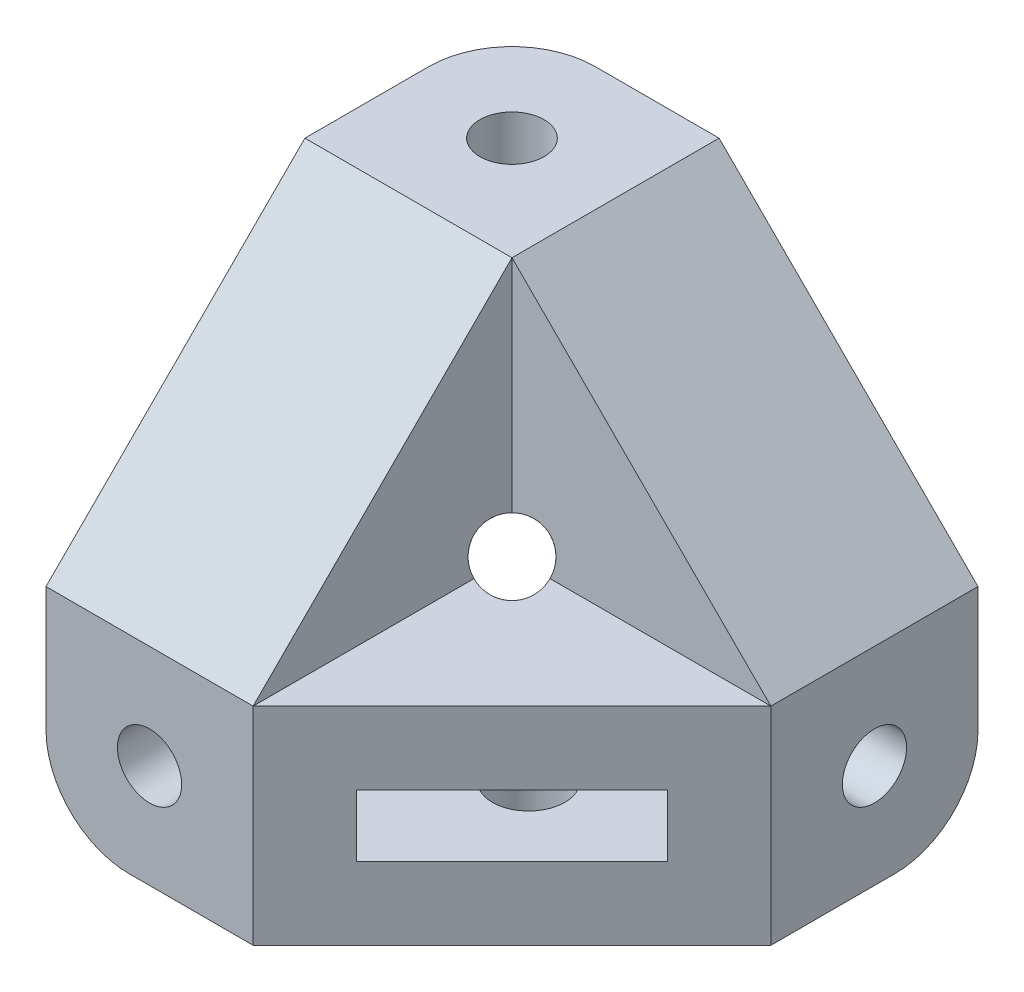
SolidWorks part; units mm, degrees
ref_plane "Front Plane" through (0, 0, 0) normal (0, 0, 1) x (1, 0, 0)
ref_plane "Top Plane" through (0, 0, 0) normal (0, 1, 0) x (1, 0, 0)
ref_plane "Right Plane" through (0, 0, 0) normal (1, 0, 0) x (0, 0, -1)
ref_plane "Plano1" through (0, 0, 20) normal (0, 0, 1) x (1, 0, 0)
sketch "Esboço1" plane through (0, 0, 20) normal (0, 0, 1) x (1, 0, 0)
  line L0 (9.638, 11.6423) -> (9.638, 56.6423)
  line L1 (9.638, 56.6423) -> (-35.362, 56.6423)
  line L2 (-35.362, 56.6423) -> (-35.362, 11.6423)
  line L3 (-35.362, 11.6423) -> (9.638, 11.6423)
extrude "Ressalto-extrusão1" add sketch "Esboço1" against normal blind 20
sketch "Esboço2" plane through (0, 0, 0) normal (0, 0, -1) x (-1, 0, 0)
  line L0 (15.362, 31.6423) -> (15.362, 56.6423)
  line L1 (15.362, 56.6423) -> (-9.638, 56.6423)
  line L2 (-9.638, 56.6423) -> (-9.638, 31.6423)
  line L3 (-9.638, 31.6423) -> (15.362, 31.6423)
extrude "Corte-extrusão1" cut sketch "Esboço2" against normal through all
sketch "Esboço3" plane through (0, 0, 20) normal (0, 0, 1) x (1, 0, 0)
  line L0 (-35.362, 31.6423) -> (-15.362, 31.6423)
  line L1 (-15.362, 31.6423) -> (-15.362, 11.6423)
  line L2 (-15.362, 11.6423) -> (-35.362, 11.6423)
  line L3 (-35.362, 11.6423) -> (-35.362, 31.6423)
extrude "Ressalto-extrusão2" add sketch "Esboço3" along normal blind 25
hole_wizard "Furo de diâmetro Ø6.2 (6.2)1" positions "Esboço5" profile "Esboço4" hole size "Ø6.2" standard "Ansi Metric"
sketch "Esboço5" plane through (9.638, 0, 0) normal (1, 0, 0) x (0, 0, -1)
  point P0 (-10, 21.6423)
sketch "Esboço4" plane through (9.638, 21.6423, 10) normal (0, 1, 0) x (0, 0, -1)
  line L0 (0, 0) -> (0, 35)
  line L1 (0, 35) -> (3.1, 35)
  line L2 (3.1, 35) -> (3.1, 0)
  line L5 (3.1, 0) -> (0, 0)
  line L10 (0, 35) -> (-3.1, 35) construction
  line L11 (0, -6.35) -> (0, 107.95) construction
  dimension "Hole Dia." = 6.2
  dimension "Hole Depth" = 35
  dimension "Drill Angle" = 180
hole_wizard "Furo de diâmetro Ø6.2 (6.2)2" positions "Esboço7" profile "Esboço6" hole size "Ø6.2" standard "Ansi Metric"
sketch "Esboço7" plane through (0, 56.6423, 0) normal (0, 1, 0) x (1, 0, 0)
  point P0 (-25.362, -10)
sketch "Esboço6" plane through (-25.362, 56.6423, 10) normal (1, 0, 0) x (0, 0, 1)
  line L0 (0, 0) -> (0, 35)
  line L1 (0, 35) -> (3.1, 35)
  line L2 (3.1, 35) -> (3.1, 0)
  line L5 (3.1, 0) -> (0, 0)
  line L10 (0, 35) -> (-3.1, 35) construction
  line L11 (0, -6.35) -> (0, 107.95) construction
  dimension "Hole Dia." = 6.2
  dimension "Hole Depth" = 35
  dimension "Drill Angle" = 180
hole_wizard "Furo de diâmetro Ø6.2 (6.2)3" positions "Esboço9" profile "Esboço8" hole size "Ø6.2" standard "Ansi Metric"
sketch "Esboço9" plane through (0, 0, 45) normal (0, 0, 1) x (1, 0, 0)
  point P0 (-25.362, 21.6423)
sketch "Esboço8" plane through (-25.362, 21.6423, 45) normal (1, 0, 0) x (0, -1, 0)
  line L0 (0, 0) -> (0, 35)
  line L1 (0, 35) -> (3.1, 35)
  line L2 (3.1, 35) -> (3.1, 0)
  line L5 (3.1, 0) -> (0, 0)
  line L10 (0, 35) -> (-3.1, 35) construction
  line L11 (0, -6.35) -> (0, 107.95) construction
  dimension "Hole Dia." = 6.2
  dimension "Hole Depth" = 35
  dimension "Drill Angle" = 180
fillet "Filete1" [suppressed] radius 4
fillet "Filete2" radius 8 3 edges at (-12.862, 11.6423, 0) (-35.362, 34.1423, 0) (-35.362, 11.6423, 22.5)
chamfer "Chanfro1" distance 25 angle 45 1 edges at (-25.362, 31.6423, 20)
chamfer "Chanfro2" distance 25 angle 45 1 edges at (-15.362, 31.6423, 10)
sketch "Esboço10" plane through (0, 11.6423, 0) normal (0, -1, 0) x (1, 0, 0)
  line L0 (-15.362, 45) -> (9.638, 20)
  line L1 (9.638, 20) -> (-15.362, 20)
  line L2 (-15.362, 20) -> (-15.362, 45)
extrude "Ressalto-extrusão3" add sketch "Esboço10" against normal blind 20
ref_plane "Plano2" through (20.4267, 20.4267, 20.4267) normal (-0.5774, -0.5774, -0.5774) x (-0.8165, 0.4082, 0.4082)
sketch "Esboço12" plane through (20.4267, 20.4267, 20.4267) normal (-0.5774, -0.5774, -0.5774) x (-0.8165, 0.4082, 0.4082)
  circle A0 centre (33.6259, 8.2323) radius 3
  dimension "D1" = 6
extrude "Corte-extrusão2" cut sketch "Esboço12" along normal through all
ref_plane "Plano3" through (0, 21.6423, 0) normal (0, -1, 0) x (-1, 0, 0)
sketch "Esboço16" plane through (0, 21.6423, 0) normal (0, -1, 0) x (-1, 0, 0)
  line L0 (10.362, -40) -> (17.262, -33.1)
  line L1 (-9.638, -20) -> (15.362, -45) construction
  line L2 (17.262, -33.1) -> (17.262, -18.1)
  line L3 (17.262, -18.1) -> (-4.638, -18.1)
  line L4 (-4.638, -18.1) -> (-4.638, -25)
  line L5 (-4.638, -25) -> (10.362, -40)
  line L7 (22.262, -14.0585) -> (22.262, -45) construction
  line L8 (-9.638, -13.1) -> (21.3036, -13.1) construction
  circle A0 centre (6.9068, -25) radius 6.5 construction
  dimension "D1" = 13
  dimension "D2" = 5
  dimension "D3" = 5
  dimension "D4" = 5
  dimension "D5" = 5
extrude "Corte-extrusão5" cut sketch "Esboço16" against normal blind 3 and the other way blind 3
sketch "Esboço17" plane through (0, 11.6423, 0) normal (0, -1, 0) x (1, 0, 0)
  line L2 (-27.362, 45) -> (-27.362, 8) construction
  circle A0 centre (-7.362, 25.5) radius 3.5
  circle A1 centre (-7.362, 25.5) radius 6.5 construction
  dimension "D1" = 7
  dimension "D4" = 13
  dimension "D2" = 20
  dimension "D3" = 17.5
sketch "Esboço18" plane through (0, 18.6423, 0) normal (0, 1, 0) x (1, 0, 0)
  line L0 (4.638, -18.1) -> (4.638, -25) construction
  line L1 (4.638, -25) -> (-10.362, -40) construction
  line L2 (-10.362, -40) -> (-17.262, -33.1) construction
  line L3 (-17.262, -33.1) -> (-17.262, -18.1) construction
  line L4 (-17.262, -18.1) -> (4.638, -18.1) construction
  line L5 (4.638, -18.1) -> (4.638, -25) construction
  line L6 (4.638, -25) -> (-10.362, -40) construction
  line L7 (-10.362, -40) -> (-17.262, -33.1) construction
  line L8 (-17.262, -33.1) -> (-17.262, -18.1) construction
  line L9 (-17.262, -18.1) -> (4.638, -18.1) construction
  line L10 (-27.362, -45) -> (-15.362, -45) construction
  line L11 (-3.262, -21.8246) -> (-8.762, -18.6491) construction
  line L12 (-8.762, -18.6491) -> (-14.262, -21.8246) construction
  line L13 (-14.262, -21.8246) -> (-14.262, -28.1754) construction
  line L14 (-14.262, -28.1754) -> (-8.762, -31.3509) construction
  line L15 (-8.762, -31.3509) -> (-3.262, -28.1754) construction
  line L16 (-3.262, -28.1754) -> (-3.262, -21.8246) construction
  circle A0 centre (-8.762, -25) radius 5.5 construction
  circle A1 centre (-8.762, -25) radius 3.5
  dimension "D1" = 11
  dimension "D2" = 7
  dimension "D3" = 3
  dimension "D4" = 20
extrude "Corte-extrusão6" cut sketch "Esboço18" against normal through all
